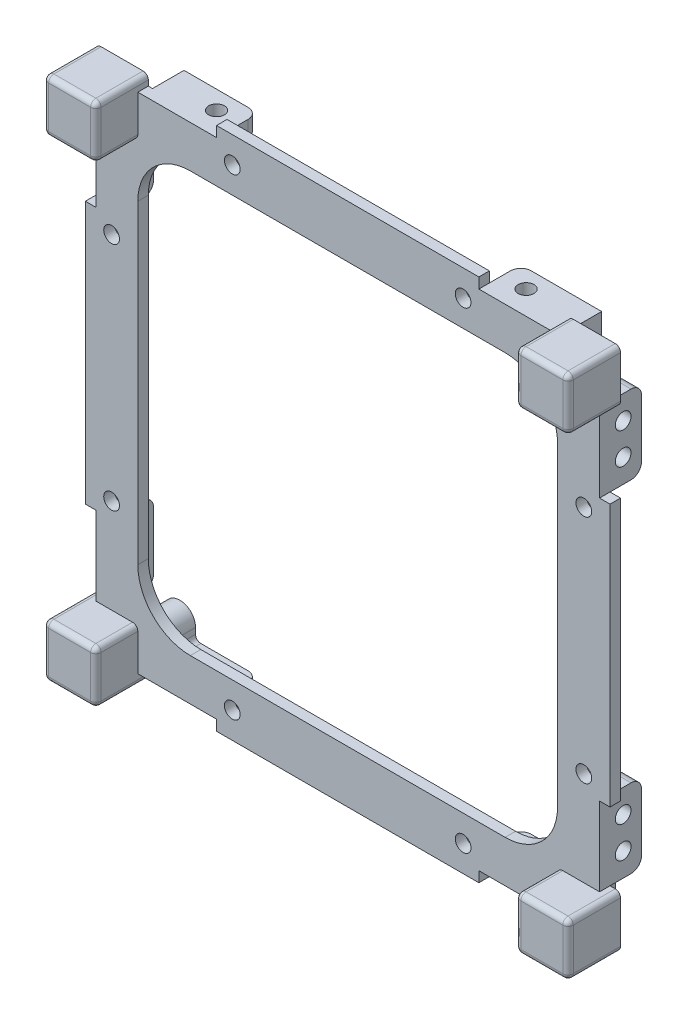
SolidWorks part; units mm, degrees
material "6061-T4 (SS)"
ref_plane "Front Plane" through (0, 0, 0) normal (0, 0, 1) x (1, 0, 0)
ref_plane "Top Plane" through (0, 0, 0) normal (0, 1, 0) x (1, 0, 0)
ref_plane "Right Plane" through (0, 0, 0) normal (1, 0, 0) x (0, 0, -1)
sketch "Sketch1" plane through (0, 0, 0) normal (0, 0, 1) x (1, 0, 0)
  line L0 (-50, 40) -> (-48, 40)
  line L1 (-49, -50) -> (-40, -50)
  line L2 (-50, -49) -> (-50, -40)
  line L3 (-49, 50) -> (-40, 50)
  line L4 (50, -49) -> (50, -40)
  line L5 (-50, -50) -> (50, 50) construction
  line L6 (-50, 50) -> (50, -50) construction
  line L7 (-30, -40) -> (30, -40)
  line L8 (-40, -30) -> (-40, 30)
  line L9 (-30, 40) -> (30, 40)
  line L10 (40, -30) -> (40, 30)
  line L11 (-40, -40) -> (40, 40) construction
  line L12 (-40, 40) -> (40, -40) construction
  line L13 (-48, 40) -> (-48, 25)
  line L14 (-48, 25) -> (-50, 25)
  line L15 (0, 50) -> (0, -50) construction
  line L16 (50, 0) -> (-50, 0) construction
  line L17 (48, 25) -> (50, 25)
  line L18 (48, 40) -> (48, 25)
  line L19 (50, 40) -> (48, 40)
  line L20 (50, -40) -> (48, -40)
  line L21 (48, -40) -> (48, -25)
  line L22 (48, -25) -> (50, -25)
  line L23 (-48, -25) -> (-50, -25)
  line L24 (-48, -40) -> (-48, -25)
  line L25 (-50, -40) -> (-48, -40)
  line L26 (50, 40) -> (50, 49)
  line L27 (-50, 40) -> (-50, 49)
  line L28 (-50, -25) -> (-50, 25)
  line L29 (50, -25) -> (50, 25)
  line L30 (-50, 22) -> (-40, 22) construction
  line L31 (-40, 50) -> (-40, 48)
  line L32 (-40, 48) -> (-25, 48)
  line L33 (-25, 48) -> (-25, 50)
  line L34 (-25, 50) -> (25, 50)
  line L35 (-22, 50) -> (-22, 40) construction
  line L36 (25, 48) -> (25, 50)
  line L37 (40, 48) -> (25, 48)
  line L38 (40, 50) -> (40, 48)
  line L39 (22, 50) -> (22, 40) construction
  line L40 (40, 50) -> (49, 50)
  line L41 (50, 22) -> (40, 22) construction
  line L42 (22, -50) -> (22, -40) construction
  line L43 (50, -22) -> (40, -22) construction
  line L44 (40, -50) -> (40, -48)
  line L45 (40, -48) -> (25, -48)
  line L46 (25, -48) -> (25, -50)
  line L47 (-22, -50) -> (-22, -40) construction
  line L48 (-25, -48) -> (-25, -50)
  line L49 (-40, -48) -> (-25, -48)
  line L50 (-40, -50) -> (-40, -48)
  line L51 (-50, -22) -> (-40, -22) construction
  line L52 (-25, -50) -> (25, -50)
  line L53 (40, -50) -> (49, -50)
  arc A0 (-49, -50) -> (-50, -49) centre (-49, -49) cw
  arc A1 (49, -50) -> (50, -49) centre (49, -49) ccw
  arc A2 (50, 49) -> (49, 50) centre (49, 49) ccw
  arc A3 (-49, 50) -> (-50, 49) centre (-49, 49) ccw
  arc A4 (-30, -40) -> (-40, -30) centre (-30, -30) cw
  arc A5 (30, -40) -> (40, -30) centre (30, -30) ccw
  arc A6 (40, 30) -> (30, 40) centre (30, 30) ccw
  arc A7 (-30, 40) -> (-40, 30) centre (-30, 30) ccw
  circle A8 centre (-45, 22) radius 1.5
  circle A9 centre (-22, 45) radius 1.5
  circle A10 centre (22, 45) radius 1.5
  circle A11 centre (45, 22) radius 1.5
  circle A12 centre (45, -22) radius 1.5
  circle A13 centre (22, -45) radius 1.5
  circle A14 centre (-22, -45) radius 1.5
  circle A15 centre (-45, -22) radius 1.5
  point P0 (0, 0)
  point P18 (0, 0)
  dimension "D2" = 1
  dimension "D3" = 10
  dimension "D9" = 3
  dimension "D1" = 100
  dimension "D4" = 10
  dimension "D5" = 15
  dimension "D6" = 2
  dimension "D7" = 10
  dimension "D8" = 100
  dimension "D10" = 28
  dimension "D11" = 10
  dimension "D12" = 28
extrude "Boss-Extrude1" add sketch "Sketch1" along normal blind 2
sketch "Sketch2" plane through (0, 0, 2) normal (0, 0, 1) x (1, 0, 0)
  line L0 (-50, 49) -> (-50, 40) construction
  line L1 (-49, 50) -> (-40, 50)
  line L2 (-50, 49) -> (-50, 40)
  line L3 (-50, 40) -> (-40, 40)
  line L4 (-40, 50) -> (-40, 40)
  line L5 (-50, 50) -> (-40, 40) construction
  line L6 (-50, 40) -> (-40, 50) construction
  line L7 (-40, 50) -> (-49, 50) construction
  line L8 (0, 50) -> (0, -50) construction
  line L9 (25, 50) -> (-25, 50) construction
  line L10 (-25, -50) -> (25, -50) construction
  line L11 (-50, 0) -> (50, 0) construction
  line L12 (-50, 25) -> (-50, -25) construction
  line L13 (50, -25) -> (50, 25) construction
  line L14 (50, 40) -> (40, 50) construction
  line L15 (50, 50) -> (40, 40) construction
  line L16 (40, 50) -> (40, 40)
  line L17 (50, 40) -> (40, 40)
  line L18 (50, 49) -> (50, 40)
  line L19 (49, 50) -> (40, 50)
  line L20 (50, -50) -> (40, -40) construction
  line L21 (50, -40) -> (40, -50) construction
  line L22 (-50, -40) -> (-40, -50) construction
  line L23 (-50, -50) -> (-40, -40) construction
  line L24 (49, -50) -> (40, -50)
  line L25 (50, -49) -> (50, -40)
  line L26 (50, -40) -> (40, -40)
  line L27 (40, -50) -> (40, -40)
  line L28 (-40, -50) -> (-40, -40)
  line L29 (-50, -40) -> (-40, -40)
  line L30 (-50, -49) -> (-50, -40)
  line L31 (-49, -50) -> (-40, -50)
  arc A0 (-49, 50) -> (-50, 49) centre (-49, 49) ccw
  arc A1 (49, 50) -> (50, 49) centre (49, 49) cw
  arc A2 (49, -50) -> (50, -49) centre (49, -49) ccw
  arc A3 (-49, -50) -> (-50, -49) centre (-49, -49) cw
  point P0 (-45, 45)
  point P31 (45, 45)
  point P46 (45, -45)
  point P47 (-45, -45)
  dimension "D3" = 1
  dimension "D1" = 10
  dimension "D2" = 10
extrude "Boss-Extrude3" add sketch "Sketch2" along normal blind 8
fillet "Fillet2" radius 1 32 edges at (-44.5, 50, 10) (-49.7071, 49.7071, 10) (-50, 44.5, 10) (-40, 50, 5) (-45, 40, 10) (-40, 45, 10) (-40, 40, 6) (-50, 40, 5) (-40, -50, 5) (-40, -45, 10) (-44.5, -50, 10) (-49.7071, -49.7071, 10) (-50, -44.5, 10) (-45, -40, 10) (-50, -40, 5) (-40, -40, 6) (50, -40, 5) (40, -50, 5) (40, -40, 6) (45, -40, 10) (50, -44.5, 10) (49.7071, -49.7071, 10) (44.5, -50, 10) (40, -45, 10) (40, 50, 5) (50, 40, 5) (40, 40, 6) (40, 45, 10) (49.7071, 49.7071, 10) (44.5, 50, 10) (50, 44.5, 10) (45, 40, 10)
sketch "Sketch6" plane through (0, 0, 0) normal (0, 0, -1) x (-1, 0, 0)
  line L0 (-40.4, 48) -> (-40.4, 42.85)
  line L1 (-45.1, -47.95) -> (45.1, -47.95) construction
  line L2 (-45.1, -47.95) -> (-45.1, 47.95) construction
  line L3 (-45.1, 47.95) -> (45.1, 47.95) construction
  line L4 (45.1, -47.95) -> (45.1, 47.95) construction
  line L5 (-45.1, -47.95) -> (45.1, 47.95) construction
  line L6 (-45.1, 47.95) -> (45.1, -47.95) construction
  line L7 (-34.4, 42.85) -> (-34.4, 44)
  line L8 (-33.4, 45) -> (-25, 45)
  line L9 (-25, 45) -> (-25, 48)
  line L10 (-25, 48) -> (-40.4, 48)
  line L11 (0, 0) -> (0, 47.95) construction
  line L12 (0, 0) -> (-45.1, 0) construction
  line L13 (25, 48) -> (25, 45)
  line L14 (25, 45) -> (32.2, 45)
  line L15 (33.2, 44) -> (33.2, 42.85)
  line L16 (25, 48) -> (39.2, 48)
  line L17 (39.2, 48) -> (39.2, 42.85)
  line L18 (-43, -48) -> (-43, -42.85)
  line L19 (-43, -48) -> (-25, -48)
  line L20 (-25, -48) -> (-25, -45)
  line L21 (-25, -45) -> (-36, -45)
  line L22 (-37, -44) -> (-37, -42.85)
  line L23 (25, -48) -> (25, -45)
  line L24 (25, -45) -> (36, -45)
  line L25 (37, -44) -> (37, -42.85)
  line L26 (43, -42.85) -> (43, -48)
  line L27 (43, -48) -> (25, -48)
  line L28 (40, -48) -> (25, -48) construction
  line L29 (-50, 25) -> (-48, 25) construction
  line L30 (-48, 40) -> (-45, 40)
  line L31 (-48, 40) -> (-48, 25)
  line L32 (-48, 25) -> (-45, 25)
  line L33 (-45, 40) -> (-45, 25)
  line L34 (48, 25) -> (50, 25) construction
  line L35 (48, 40) -> (45, 40)
  line L36 (48, 40) -> (48, 25)
  line L37 (48, 25) -> (45, 25)
  line L38 (45, 40) -> (45, 25)
  line L39 (-49, -40) -> (-48, -40) construction
  line L40 (-48, -25) -> (-45, -25)
  line L41 (-48, -25) -> (-48, -40)
  line L42 (-48, -40) -> (-45, -40)
  line L43 (-45, -25) -> (-45, -40)
  line L44 (48, -40) -> (49, -40) construction
  line L45 (48, -25) -> (45, -25)
  line L46 (48, -25) -> (48, -40)
  line L47 (48, -40) -> (45, -40)
  line L48 (45, -25) -> (45, -40)
  circle A0 centre (-37.4, 42.85) radius 1.5
  circle A1 centre (-40, -42.85) radius 1.5
  circle A2 centre (36.2, 42.85) radius 1.5
  circle A3 centre (40, -42.85) radius 1.5
  arc A4 (-40.4, 42.85) -> (-34.4, 42.85) centre (-37.4, 42.85) ccw
  arc A5 (-34.4, 44) -> (-33.4, 45) centre (-33.4, 44) cw
  arc A6 (33.2, 42.85) -> (39.2, 42.85) centre (36.2, 42.85) ccw
  arc A7 (33.2, 44) -> (32.2, 45) centre (32.2, 44) ccw
  arc A8 (-43, -42.85) -> (-37, -42.85) centre (-40, -42.85) cw
  arc A9 (-36, -45) -> (-37, -44) centre (-36, -44) cw
  arc A10 (37, -42.85) -> (43, -42.85) centre (40, -42.85) cw
  arc A11 (36, -45) -> (37, -44) centre (36, -44) ccw
  point P0 (0, 0)
  dimension "D3" = 3
  dimension "D10" = 3
  dimension "D11" = 1
  dimension "D13" = 1
  dimension "D14" = 3
  dimension "D15" = 1
  dimension "D18" = 3
  dimension "D19" = 1
  dimension "D1" = 95.9
  dimension "D2" = 90.2
  dimension "D4" = 82.5
  dimension "D5" = 5.1
  dimension "D6" = 8.9
  dimension "D7" = 5.1
  dimension "D8" = 85.1
  dimension "D9" = 90.8
  dimension "D12" = 3
  dimension "D16" = 3
  dimension "D17" = 3
  dimension "D20" = 3
extrude "Boss-Extrude5" add sketch "Sketch6" along normal blind 6
fillet "Fillet3" radius 2 12 edges at (46.5, -40, -6) (46.5, -25, -6) (-46.5, -40, -6) (-46.5, -25, -6) (-46.5, 25, -6) (-46.5, 40, -6) (-25, 46.5, -6) (25, 46.5, -6) (46.5, 25, -6) (46.5, 40, -6) (-25, -46.5, -6) (25, -46.5, -6)
sketch "Sketch7" plane through (0, 0, 0) normal (1, 0, 0) x (0, 0, -1)
  line L0 (6, 38) -> (6, 27) construction
  line L1 (4, 40) -> (0, 40) construction
  line L2 (0, 0) -> (9.3897, 0) construction
  circle A0 centre (2.5, 35.5) radius 1.5
  circle A1 centre (2.5, 29.5) radius 1.5
  circle A2 centre (2.5, -29.5) radius 1.5
  circle A3 centre (2.5, -35.5) radius 1.5
  dimension "D1" = 3
  dimension "D2" = 3.5
  dimension "D3" = 4.5
  dimension "D4" = 6
extrude "Cut-Extrude1" cut sketch "Sketch7" against normal through all and the other way through all
sketch "Sketch8" plane through (0, 0, 0) normal (0, 1, 0) x (1, 0, 0)
  line L0 (-39.2, 6) -> (-27, 6) construction
  line L1 (-25, 4) -> (-25, 0) construction
  line L2 (25, 4) -> (25, 0) construction
  circle A0 centre (-29.5, 2.5) radius 1.5
  circle A1 centre (29.5, 2.5) radius 1.5
  dimension "D1" = 3
  dimension "D2" = 3.5
  dimension "D3" = 4.5
  dimension "D4" = 4.5
extrude "Cut-Extrude2" cut sketch "Sketch8" against normal through all and the other way through all
